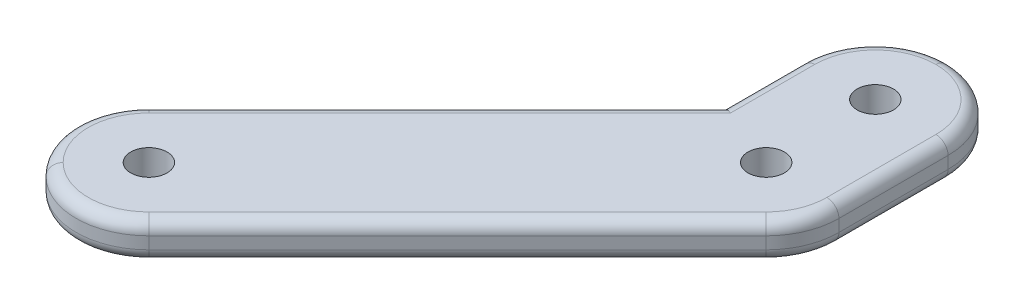
SolidWorks part; units mm, degrees
material "6061 Alloy"
ref_plane "Front Plane" through (0, 0, 0) normal (0, 0, 1) x (1, 0, 0)
ref_plane "Top Plane" through (0, 0, 0) normal (0, 1, 0) x (1, 0, 0)
ref_plane "Right Plane" through (0, 0, 0) normal (1, 0, 0) x (0, 0, -1)
sketch "Sketch1" plane through (0, 0, 0) normal (0, 1, 0) x (1, 0, 0)
  line L0 (0, 31.2053) -> (0, -31.2053) construction
  line L1 (-12.7, -31.2053) -> (12.7, -31.2053) construction
  line L2 (-12.7, -31.2053) -> (-12.7, 31.2053) construction
  line L3 (-12.7, 31.2053) -> (12.7, 31.2053)
  line L4 (12.7, -31.2053) -> (12.7, 31.2053) construction
  line L5 (-12.7, -31.2053) -> (12.7, 31.2053) construction
  line L6 (-12.7, 31.2053) -> (12.7, -31.2053) construction
  line L7 (-12.7, 4.7158) -> (-71.842, -54.4263)
  line L8 (-71.842, -54.4263) -> (-53.8815, -72.3868)
  line L9 (-53.8815, -72.3868) -> (-12.7, -31.2053)
  line L10 (-62.8618, -63.4065) -> (0, -0.5447)
  line L11 (-12.7, -31.2053) -> (8.9803, -9.525)
  line L12 (12.7, -0.5447) -> (12.7, 31.2053)
  line L13 (-12.7, 4.7158) -> (-12.7, 31.2053)
  circle A1 centre (0, -0.5447) radius 3.175
  circle A2 centre (0, 18.5053) radius 3.175
  circle A4 centre (0, -0.5447) radius 12.7
  circle A5 centre (-53.8815, -54.4263) radius 3.175
  point P0 (0, 0)
  dimension "D3" = 6.35
  dimension "D1" = 25.4
  dimension "D8" = 12.7
  dimension "D6" = 76.2
  dimension "D2" = 25.4
  dimension "D4" = 19.05
  dimension "D5" = 135
  dimension "D7" = 12.7
extrude "Boss-Extrude1" add sketch "Sketch1" along normal blind 6.35 contours A5 L10 A4 L12 L3 L13 L7 L8 A2 | A4 A1 | A5 L10 L8 L9 L11 A4 region at (-25.7104, 0, 13.0159) region at (11.4014, 0, 5.2674) region at (-29.983, 0, 39.7959)
fillet "Fillet2" radius 12.7 4 edges at (12.7, 3.175, -31.2053) (-12.7, 3.175, -31.2053) (-71.842, 3.175, 54.4263) (-53.8815, 3.175, 72.3868)
fillet "Fillet3" radius 2.1167 18 edges at (-12.7, 0, -11.6105) (-8.9803, 0, -27.4855) (8.9803, 0, -27.4855) (12.7, 0, -8.9803) (11.7333, 0, 5.4048) (-17.9605, 0, 36.4658) (-53.8815, 0, 67.1263) (-66.5815, 0, 54.4263) (-12.7, 6.35, -11.6105) (-8.9803, 6.35, -27.4855) (8.9803, 6.35, -27.4855) (12.7, 6.35, -8.9803) (11.7333, 6.35, 5.4048) (-17.9605, 6.35, 36.4658) (-53.8815, 6.35, 67.1263) (-66.5815, 6.35, 54.4263) (-37.7809, 0, 20.3651) (-37.7809, 6.35, 20.3651)
sketch "Sketch2" plane through (0, 6.35, 0) normal (0, 1, 0) x (1, 0, 0)
  line L0 (12.7, 18.5053) -> (12.7, -0.5447) construction
  line L1 (12.7, 31.2053) -> (-66.5815, 31.2053)
  line L2 (12.7, 31.2053) -> (12.7, -67.1263)
  line L3 (12.7, -67.1263) -> (-66.5815, -67.1263)
  line L4 (-66.5815, 31.2053) -> (-66.5815, -67.1263)
  line L5 (12.7, 31.2053) -> (-66.5815, -67.1263) construction
  line L6 (12.7, -67.1263) -> (-66.5815, 31.2053) construction
  arc A0 (-62.8618, -45.446) -> (-62.8618, -63.4065) centre (-53.8815, -54.4263) ccw construction
  arc A1 (-62.8618, -63.4065) -> (-44.9013, -63.4065) centre (-53.8815, -54.4263) ccw construction
  point P4 (-26.9408, -17.9605)
  dimension "D1" = 79.2815
  dimension "D2" = 98.3315
